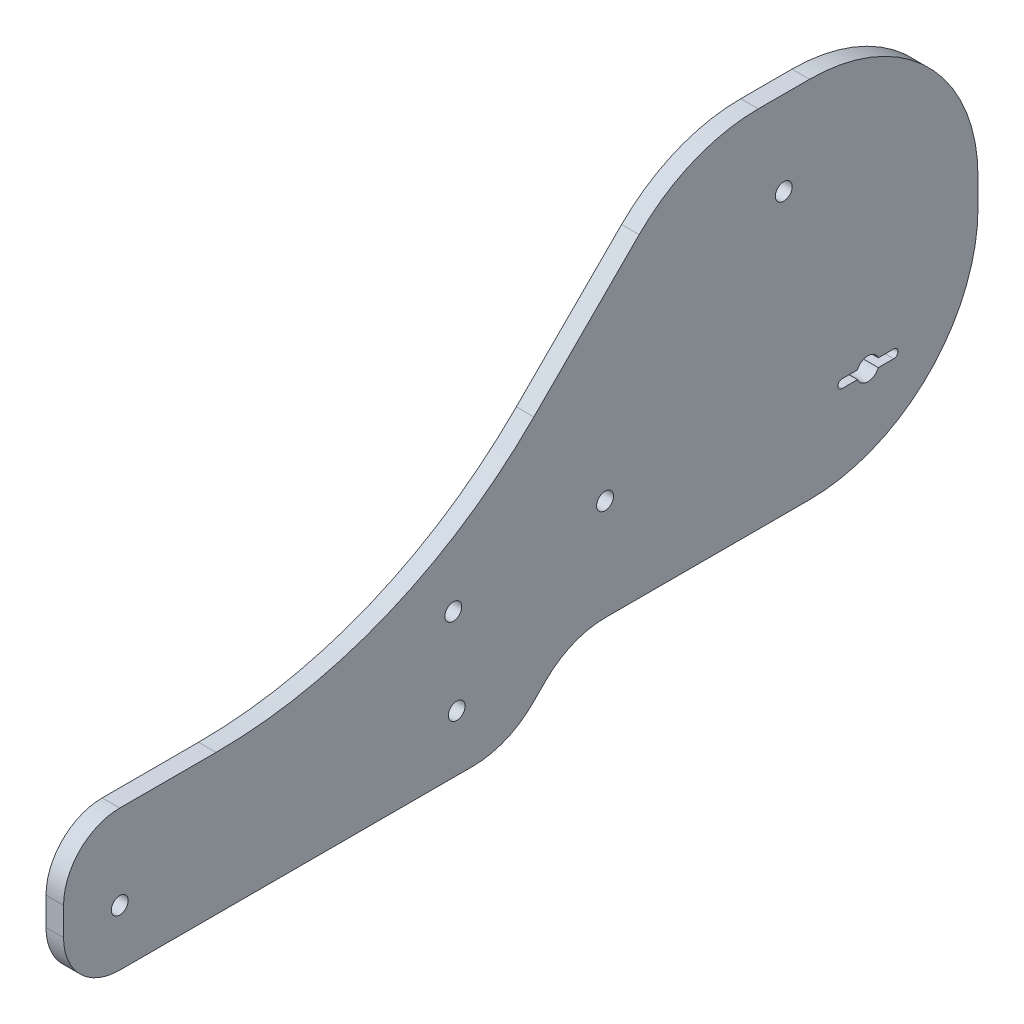
SolidWorks part; units mm, degrees
ref_plane "Front Plane" through (0, 0, 0) normal (0, 0, 1) x (1, 0, 0)
ref_plane "Top Plane" through (0, 0, 0) normal (0, 1, 0) x (1, 0, 0)
ref_plane "Right Plane" through (0, 0, 0) normal (1, 0, 0) x (0, 0, -1)
sketch "Sketch1" plane through (0, 0, 0) normal (1, 0, 0) x (0, 0, -1)
  line L0 (-62.0729, -10) -> (29.851, 81.9239) construction
  line L1 (29.851, 81.9239) -> (22.0729, 89.7021) construction
  line L2 (22.0729, 89.7021) -> (-69.851, -2.2218) construction
  line L3 (-69.851, -2.2218) -> (-62.0729, -10) construction
  line L4 (-4.6, 0) -> (4.6, 0) construction
  line L5 (-6, 5) -> (-6, -5) construction
  line L6 (-4.6, 0.75) -> (-1.854, 0.75)
  line L7 (-4.6, -0.75) -> (-1.854, -0.75)
  line L8 (-6, -5) -> (6, -5) construction
  line L9 (1.854, 0.75) -> (4.6, 0.75)
  line L10 (1.854, -0.75) -> (4.6, -0.75)
  line L11 (6, -5) -> (6, 5) construction
  line L12 (6, 5) -> (-6, 5) construction
  line L13 (-6, 5) -> (6, -5) construction
  line L14 (-69.851, -2.2218) -> (29.851, 81.9239) construction
  line L15 (-20, 39.851) -> (-20, 79.8794) construction
  line L16 (-9.747, 57.8823) -> (-1.9688, 50.1041) construction
  line L17 (-46.7993, 3.0108) -> (-14.9795, 34.8306) construction
  line L18 (-73.2042, -16.1314) -> (-133.2042, -16.1314) construction
  line L19 (-73.8108, -0.5248) -> (-63.2042, -11.1314) construction
  line L20 (-62.0729, -10) -> (-63.2042, -11.1314) construction
  line L21 (-143.2042, -1.1314) -> (-143.2042, -26.1314)
  line L22 (-143.2042, -26.1314) -> (-64.0621, -26.1314)
  line L23 (-64.0621, -26.1314) -> (-52.9307, -15)
  line L24 (-52.9307, -15) -> (19.6, -15)
  line L25 (19.6, -15) -> (19.6, 49.8306)
  line L26 (19.6, 49.8306) -> (-31.9408, 49.8306)
  line L27 (-31.9408, 49.8306) -> (-82.9027, -1.1314)
  line L28 (-82.9027, -1.1314) -> (-143.2042, -1.1314)
  line L29 (0, -31) -> (-153.4899, -31) construction
  arc A0 (-1.854, -0.75) -> (1.854, -0.75) centre (0, 0) ccw
  arc A1 (-4.6, 0.75) -> (-4.6, -0.75) centre (-4.6, 0) ccw
  arc A2 (1.854, 0.75) -> (-1.854, 0.75) centre (0, 0) ccw
  circle A3 centre (0, 0) radius 31 construction
  arc A4 (4.6, -0.75) -> (4.6, 0.75) centre (4.6, 0) ccw
  circle A5 centre (-46.7993, 3.0108) radius 1.5
  circle A6 centre (-14.9795, 34.8306) radius 1.5
  circle A7 centre (-73.8108, -0.5248) radius 1.5
  circle A8 centre (-73.2042, -16.1314) radius 1.5
  circle A9 centre (-133.2042, -16.1314) radius 1.5
  point P11 (-4.6, 0)
  point P16 (4.6, 0)
  point P43 (-60.3276, -26.1314)
  dimension "D4" = 4
  dimension "D5" = 0.75
  dimension "D9" = 62
  dimension "D14" = 3
  dimension "D15" = 1.6
  dimension "D1" = 11
  dimension "D2" = 130
  dimension "D3" = 9.2
  dimension "D6" = 10
  dimension "D7" = 12
  dimension "D8" = 45
  dimension "D10" = 20
  dimension "D11" = 10
  dimension "D12" = 45
  dimension "D13" = 1.6
  dimension "D16" = 20
  dimension "D17" = 65
  dimension "D18" = 15
  dimension "D19" = 5
  dimension "D20" = 10
  dimension "D21" = 60
  dimension "D22" = 10
  dimension "D23" = 15
  dimension "D24" = 10
  dimension "D25" = 15
  dimension "D26" = 10
  dimension "D27" = 15
  dimension "D28" = 15
  dimension "D29" = 10
extrude "Boss-Extrude1" add sketch "Sketch1" along normal blind 3.125
fillet "Fillet1" radius 10 2 edges at (1.5625, -1.1314, 143.2042) (1.5625, -26.1314, 143.2042)
fillet "Fillet2" radius 15 2 edges at (1.5625, -26.1314, 64.0621) (1.5625, -15, 52.9307)
fillet "Fillet3" radius 30 1 edges at (1.5625, -15, -19.6)
fillet "Fillet4" radius 30 1 edges at (1.5625, 49.8306, 31.9408)
fillet "Fillet5" radius 80 1 edges at (1.5625, -1.1314, 82.9027)
fillet "Fillet6" radius 30 1 edges at (1.5625, 49.8306, -19.6)
